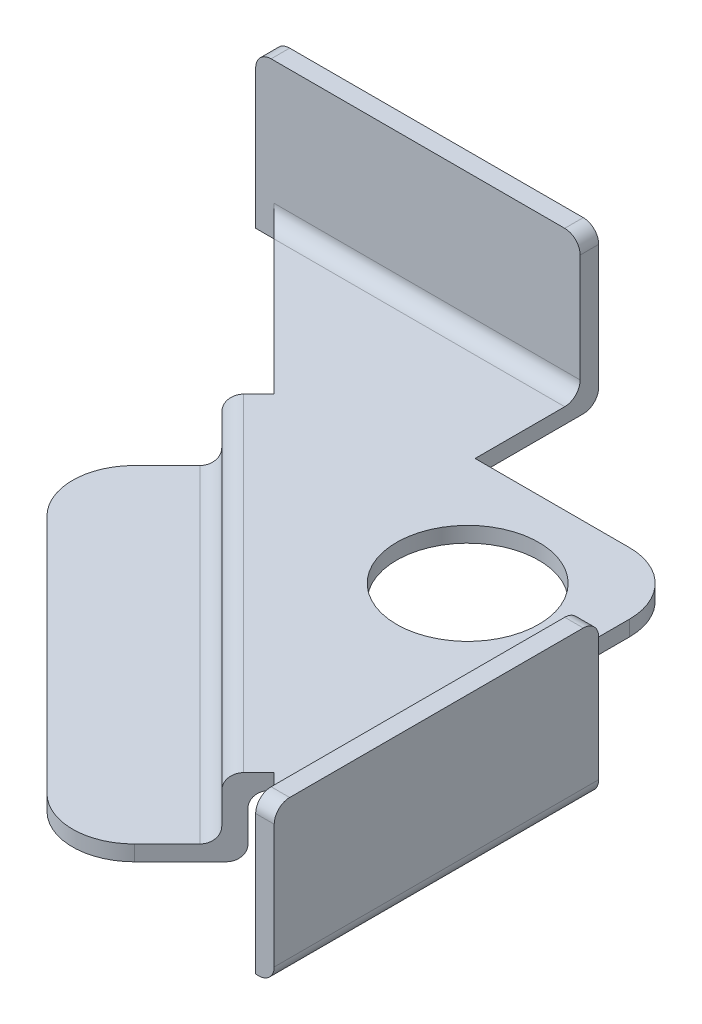
SolidWorks part; units mm, degrees
ref_plane "Front Plane" through (0, 0, 0) normal (0, 0, 1) x (1, 0, 0)
ref_plane "Top Plane" through (0, 0, 0) normal (0, 1, 0) x (1, 0, 0)
ref_plane "Right Plane" through (0, 0, 0) normal (1, 0, 0) x (0, 0, -1)
sketch "Sketch1" plane through (0, 0, 0) normal (0, 1, 0) x (1, 0, 0)
  line L1 (0, 0) -> (21.5, 0)
  line L2 (0, 0) -> (0, 21.5)
  line L3 (0, 21.5) -> (21.5, 21.5)
  line L4 (21.5, 0) -> (21.5, 21.5)
  dimension "D1" = 21.5
  dimension "D2" = 21.5
extrude "Boss-Extrude1" add sketch "Sketch1" along normal blind 0.5
sketch "Sketch2" plane through (0, 0.5, 0) normal (0, 1, 0) x (1, 0, 0)
  line L0 (0, 21.5) -> (21.5, 0)
  line L1 (21.5, 21.5) -> (17.5, 21.5)
  line L2 (21.5, 21.5) -> (21.5, 10.5)
  line L3 (21.5, 10.5) -> (17.5, 10.5)
  line L4 (17.5, 21.5) -> (17.5, 10.5)
  line L5 (21.5, 21.5) -> (10.5, 21.5)
  line L6 (21.5, 21.5) -> (21.5, 17.5)
  line L7 (21.5, 17.5) -> (10.5, 17.5)
  line L8 (10.5, 21.5) -> (10.5, 17.5)
  line L9 (21.5, 0) -> (0, 0)
  line L10 (0, 0) -> (0, 21.5)
  circle A0 centre (13.88, 13.88) radius 2.3
  line M7 (0, 21.5) -> (0, 0)
  line M8 (0, 0) -> (21.5, 0)
  line M9 (21.5, 0) -> (21.5, 21.5)
  line M10 (21.5, 21.5) -> (0, 21.5)
  dimension "D5" = 3.62
  dimension "D1" = 4
  dimension "D2" = 11
  dimension "D3" = 4
  dimension "D4" = 11
  dimension "D6" = 3.62
extrude "Cut-Extrude1" cut sketch "Sketch2" against normal through all contours L0 M7 M8 | A0 | L7 L2 L4 M10 | L7 L4 L3 M9 | L8 L7 L4 M10 region at (7.1667, 0.5, -7.1667) region at (14, 0.5, -19.5) region at (19.5, 0.5, -14) region at (19.5, 0.5, -19.5) region at (13.88, 0.5, -13.88)
fillet "Fillet1" radius 2 1 edges at (17.5, 0.25, -17.5)
sketch "Sketch3" plane through (0, 0.5, 0) normal (0, 1, 0) x (1, 0, 0)
  line L1 (21.5, 10.5) -> (20.9, 10.5)
  line L2 (21.5, 10.5) -> (21.5, 0)
  line L3 (21.5, 0) -> (20.9, 0)
  line L4 (20.9, 10.5) -> (20.9, 0)
  line L5 (10.5, 21.5) -> (0, 21.5)
  line L6 (10.5, 21.5) -> (10.5, 20.9)
  line L7 (10.5, 20.9) -> (0, 20.9)
  line L8 (0, 21.5) -> (0, 20.9)
  dimension "D1" = 0.6
  dimension "D2" = 0.6
extrude "Boss-Extrude2" add sketch "Sketch3" along normal blind 4.5 and the other way blind 0.5
fillet "Fillet11" radius 0.5 8 edges at (5.55, 0.5, -20.9) (0, 5, -21.2) (21.2, 5, 0) (21.2, 5, -10.5) (10.5, 5, -21.2) (5.25, 0, -21.5) (21.5, 0, -5.25) (20.9, 0.5, -5.55)
sketch "Sketch6" plane through (10.75, 0, -10.75) normal (-0.7071, 0, 0.7071) x (0.7071, 0, 0.7071)
  line L0 (-13.6472, 0.5) -> (13.6472, 0.5) construction
  line L1 (-7.5, 0.5) -> (7.5, 0.5)
  line L2 (-7.5, 0.5) -> (-7.5, 0)
  line L3 (-7.5, 0) -> (7.5, 0)
  line L4 (7.5, 0.5) -> (7.5, 0)
  line L5 (-14.3543, 0) -> (14.3543, 0) construction
  dimension "D1" = 15
  dimension "D2" = 7.5
extrude "Boss-Extrude3" add sketch "Sketch6" along normal blind 1.2
sketch "Sketch8" plane through (0, 0, 0) normal (0, -1, 0) x (1, 0, 0)
  line L0 (4.5982, -15.2048) -> (15.2048, -4.5982)
  line L1 (15.2048, -4.5982) -> (15.629, -5.0224)
  line L2 (15.2048, -4.5982) -> (16.0533, -5.4467) construction
  line L3 (15.629, -5.0224) -> (5.0224, -15.629)
  line L4 (4.5982, -15.2048) -> (5.4467, -16.0533) construction
  line L5 (5.0224, -15.629) -> (4.5982, -15.2048)
extrude "Boss-Extrude4" add sketch "Sketch8" along normal blind 2
sketch "Sketch9" plane through (9.9015, 0, -9.9015) normal (-0.7071, 0, 0.7071) x (0.7071, 0, 0.7071)
  line L0 (7.5, -2) -> (7.5, 0.5) construction
  line L1 (-7.5, -2) -> (7.5, -2)
  line L2 (-7.5, -2) -> (-7.5, -1.5)
  line L3 (-7.5, -1.5) -> (7.5, -1.5)
  line L4 (7.5, -2) -> (7.5, -1.5)
  dimension "D1" = 0.5
extrude "Boss-Extrude5" add sketch "Sketch9" along normal blind 4
fillet "Fillet12" radius 0.5 4 edges at (10.3257, 0, -10.3257) (10.3257, -2, -10.3257) (9.9015, 0.5, -9.9015) (9.9015, -1.5, -9.9015)
fillet "Fillet13" radius 2 2 edges at (12.3763, -1.75, -1.7697) (1.7697, -1.75, -12.3763)
